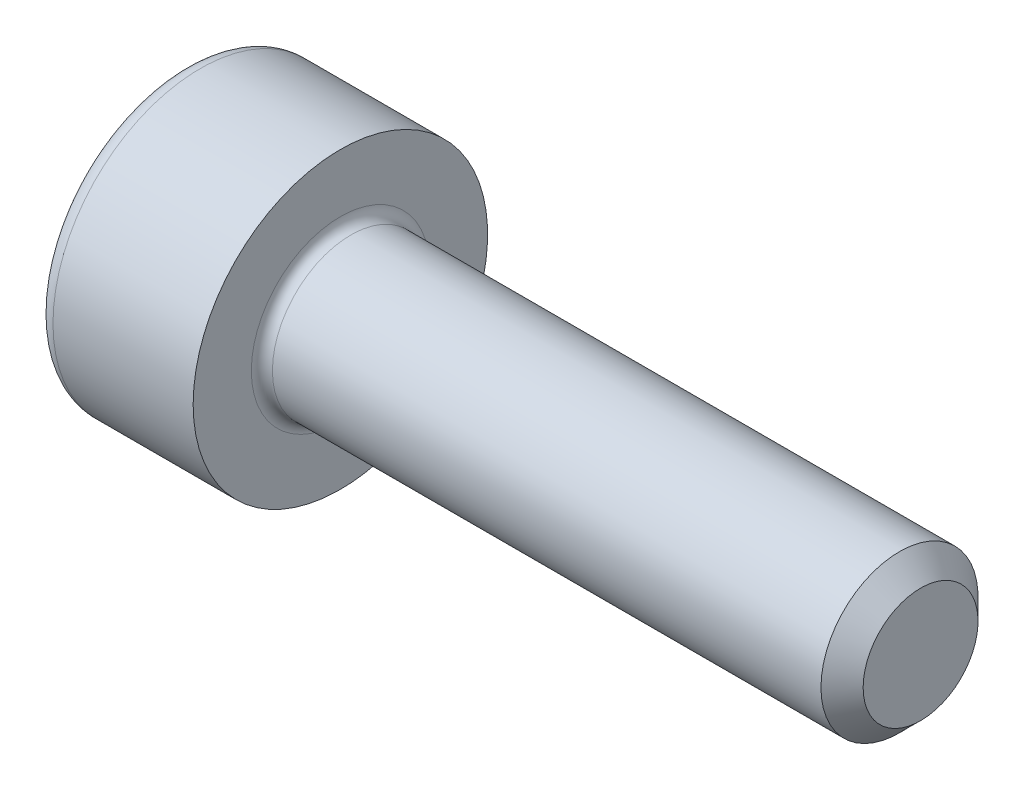
SolidWorks part; units mm, degrees
ref_plane "Спереди" through (0, 0, 0) normal (0, 0, 1) x (1, 0, 0)
ref_plane "Сверху" through (0, 0, 0) normal (0, 1, 0) x (1, 0, 0)
ref_plane "Справа" through (0, 0, 0) normal (1, 0, 0) x (0, 0, -1)
sketch "Sketch1" plane through (0, 0, 0) normal (0, 0, 1) x (1, 0, 0)
  line L0 (0, 0) -> (1.4887, 0)
  line L1 (1.4887, 0) -> (1.4887, 1.3957)
  line L2 (1.4887, 1.3957) -> (0, 1.3957)
  line L3 (0, 1.3957) -> (0, 0)
  line L4 (1.4887, 0) -> (6.9887, 0)
  line L5 (6.9887, 0) -> (6.9887, 0.7444)
  line L6 (6.9887, 0.7444) -> (1.4887, 0.7444)
  dimension "D1" = 5.5
revolve "Revolve1" add sketch "Sketch1" angle 360 about L0 region at (0.7444, 0.6978, 0) region at (4.2387, 0.3722, 0)
fillet "Fillet1" radius 0.1 1 edges at (1.4887, 0, 0.7444)
fillet "Fillet2" radius 0.16 1 edges at (0, 0, 1.3957)
chamfer "Chamfer1" distance 0.2 angle 45 1 edges at (6.9887, 0, 0.7444)
sketch "Sketch2" plane through (0, 0, 0) normal (-1, 0, 0) x (0, 0, 1)
  line L1 (0, 0.8776) -> (-0.76, 0.4388)
  line L2 (-0.76, 0.4388) -> (-0.76, -0.4388)
  line L3 (-0.76, -0.4388) -> (0, -0.8776)
  line L4 (0, -0.8776) -> (0.76, -0.4388)
  line L5 (0.76, -0.4388) -> (0.76, 0.4388)
  line L6 (0.76, 0.4388) -> (0, 0.8776)
  circle A0 centre (0, 0) radius 0.76 construction
extrude "Extrude1" cut sketch "Sketch2" against normal blind 0.7
